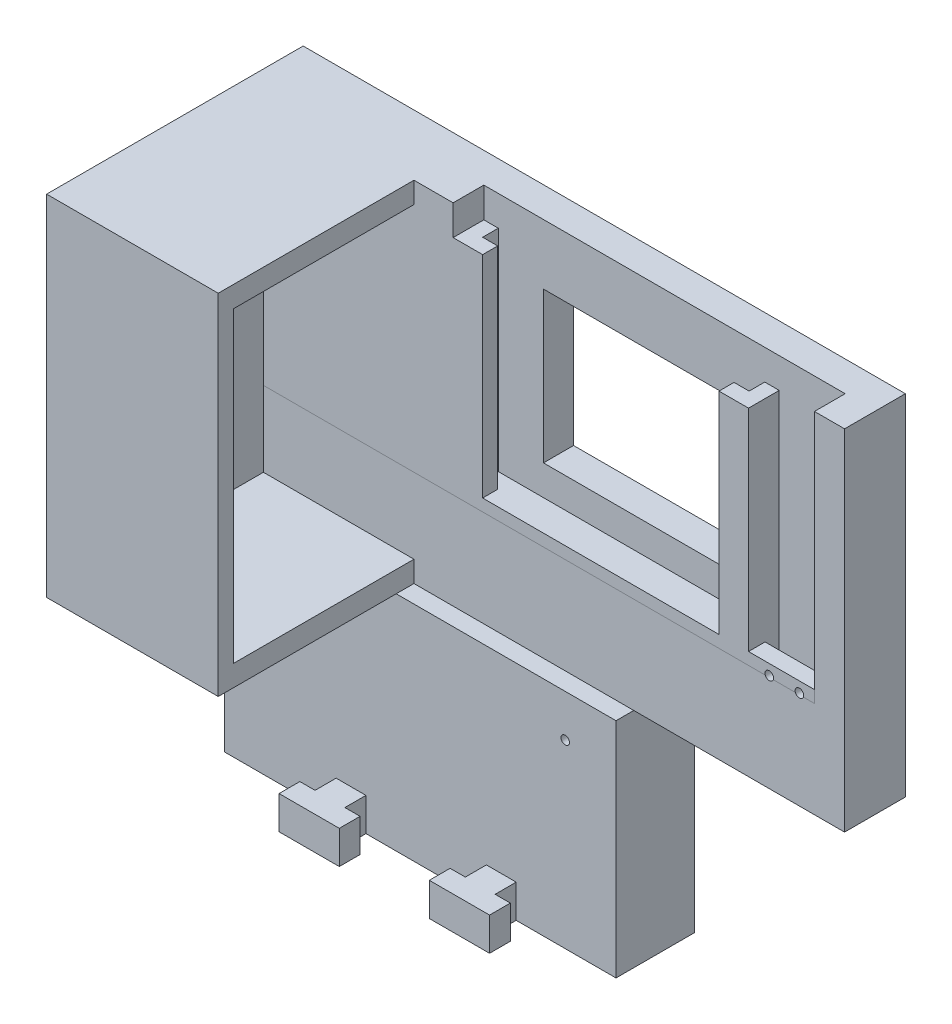
SolidWorks part; units mm, degrees
ref_plane "Front Plane" through (0, 0, 0) normal (0, 0, 1) x (1, 0, 0)
ref_plane "Top Plane" through (0, 0, 0) normal (0, 1, 0) x (1, 0, 0)
ref_plane "Right Plane" through (0, 0, 0) normal (1, 0, 0) x (0, 0, -1)
sketch "Sketch1" plane through (0, 0, 0) normal (0, 0, 1) x (1, 0, 0)
  line L1 (-95, -40) -> (95, -40)
  line L2 (-95, -40) -> (-95, 40)
  line L3 (-95, 40) -> (95, 40)
  line L4 (95, -40) -> (95, 40)
  line L5 (-95, -40) -> (95, 40) construction
  line L6 (-95, 40) -> (95, -40) construction
  point P0 (0, 0)
  dimension "D1" = 0
  dimension "D2" = 190
  dimension "80" = 80
extrude "Boss-Extrude1" add sketch "Sketch1" along normal blind 10
sketch "Sketch2" plane through (0, -40, 0) normal (0, -1, 0) x (1, 0, 0)
  line L0 (-95, 10) -> (95, 10) construction
  line L1 (-25, 10) -> (-20.2, 10)
  line L2 (-25, 10) -> (-25, 15.2)
  line L3 (-25, 15.2) -> (-20.2, 15.2)
  line L4 (-20.2, 10) -> (-20.2, 15.2)
  line L5 (-25, 20.2) -> (-15.2, 20.2)
  line L6 (-25, 20.2) -> (-25, 15.2)
  line L7 (-25, 15.2) -> (-15.2, 15.2)
  line L8 (-15.2, 20.2) -> (-15.2, 15.2)
  line L9 (73.1, 10) -> (68.3, 10)
  line L10 (73.1, 10) -> (73.1, 15.2)
  line L11 (73.1, 15.2) -> (68.3, 15.2)
  line L12 (68.3, 10) -> (68.3, 15.2)
  line L13 (63.3, 20.2) -> (73.1, 20.2)
  line L14 (63.3, 20.2) -> (63.3, 15.2)
  line L15 (63.3, 15.2) -> (73.1, 15.2)
  line L16 (73.1, 20.2) -> (73.1, 15.2)
  line L17 (-95, 10) -> (-95, 0) construction
  dimension "D1" = 0
  dimension "D2" = 0
  dimension "D3" = 0
  dimension "D4" = 5.2
  dimension "D5" = 9.8
  dimension "D6" = 5
  dimension "D7" = 4.8
  dimension "D8" = 9.8
  dimension "D9" = 5
  dimension "D10" = 0
  dimension "D11" = 0
  dimension "D12" = 0
  dimension "D13" = 5.2
  dimension "D14" = 4.8
  dimension "D15" = 88.5
  dimension "D16" = 70
extrude "Boss-Extrude2" add sketch "Sketch2" against normal blind 70 contours L8 L5 L6 L3 L7 | L16 L13 L14 L15 L11 | L4 L3 L2 L1 | L10 L11 L12 L9 region at (-20.1, -40, 17.7) region at (68.2, -40, 17.7)
sketch "Sketch3" plane through (0, 0, 10) normal (0, 0, 1) x (1, 0, 0)
  line L0 (-20.2, -40) -> (68.3, -40) construction
  line L1 (53.3, -30) -> (-5.2, -30)
  line L2 (53.3, -30) -> (53.3, 20)
  line L3 (53.3, 20) -> (-5.2, 20)
  line L4 (-5.2, -30) -> (-5.2, 20)
  line L5 (63.3, 30) -> (63.3, -40) construction
  line L6 (-15.2, 30) -> (-15.2, -40) construction
  line L7 (73.1, 30) -> (68.3, 30) construction
  dimension "D1" = 10
  dimension "D2" = 10
  dimension "D3" = 10
  dimension "D4" = 10
extrude "Cut-Extrude1" cut sketch "Sketch3" against normal blind 10
sketch "Sketch5" plane through (0, -40, 0) normal (0, -1, 0) x (-1, 0, 0)
  line L0 (25, -20.2) -> (15.2, -20.2) construction
  line L1 (95, -20.2) -> (-95, -20.2)
  line L2 (95, -20.2) -> (95, 0)
  line L3 (95, 0) -> (-95, 0)
  line L4 (-95, -20.2) -> (-95, 0)
  line L5 (95, -10) -> (95, 0) construction
  line L7 (95, 0) -> (-95, 0) construction
  line L8 (-95, -10) -> (-95, 0) construction
  dimension "D1" = 0
  dimension "D2" = 0
  dimension "D3" = 0
  dimension "D4" = 0
extrude "Boss-Extrude3" add sketch "Sketch5" along normal blind 4
sketch "Sketch6" plane through (0, 0, 0) normal (0, 0, -1) x (-1, 0, 0)
  line L0 (95, -44) -> (-95, -44) construction
  line L1 (95, -44) -> (-95, -44)
  line L2 (95, -44) -> (95, 40)
  line L3 (95, 40) -> (-95, 40)
  line L4 (-95, -44) -> (-95, 40)
  line L5 (95, -150) -> (-105, -150)
  line L6 (95, -150) -> (95, 40)
  line L7 (95, 40) -> (-105, 40)
  line L8 (-105, -150) -> (-105, 40)
  line L9 (95, 40) -> (95, -44) construction
  line L10 (-95, 40) -> (95, 40) construction
  line L11 (-95, -44) -> (-95, 40) construction
  line M5 (-95, 40) -> (-95, -44)
  line M6 (-95, -44) -> (95, -44)
  line M7 (95, -44) -> (95, 40)
  dimension "D1" = 0
  dimension "D2" = 0
  dimension "D3" = 0
  dimension "D4" = 0
  dimension "D5" = 10
  dimension "D6" = 190
  dimension "D7" = 0
  dimension "D8" = 0
extrude "Boss-Extrude5" add sketch "Sketch6" against normal blind 20.1999 contours L8 L5 L6 L7 M7 M6 M5 region at (8.6207, -93.3793, 0)
sketch "Sketch7" plane through (0, 0, 20.1999) normal (0, 0, 1) x (1, 0, 0)
  line L0 (105, -150) -> (105, 40) construction
  line L1 (105, -76) -> (-95, -76)
  line L2 (105, -76) -> (105, -150)
  line L3 (105, -150) -> (-95, -150)
  line L4 (-95, -76) -> (-95, -150)
  line L5 (70.7614, -89.3834) -> (70.4933, -89.3834)
  line L6 (70.7614, -89.3834) -> (70.7614, -108.9872)
  line L7 (70.7614, -108.9872) -> (70.4933, -108.9872)
  line L8 (70.4933, -89.3834) -> (70.4933, -108.9872)
  line L9 (-95, -150) -> (105, -150) construction
  line L10 (-95, -150) -> (-95, -44) construction
  line L11 (95, -44) -> (-95, -44) construction
  dimension "D1" = 0
  dimension "D2" = 0
  dimension "D3" = 0
  dimension "D4" = 32
extrude "Boss-Extrude6" add sketch "Sketch7" along normal blind 5.9
sketch "Sketch8" plane through (0, -150, 0) normal (0, -1, 0) x (1, 0, 0)
  line L0 (-95, 26.0999) -> (105, 26.0999) construction
  line L1 (-57.95, 33.0999) -> (-48.05, 33.0999)
  line L2 (-57.95, 33.0999) -> (-57.95, 26.0999)
  line L3 (-57.95, 26.0999) -> (-48.05, 26.0999)
  line L4 (-48.05, 33.0999) -> (-48.05, 26.0999)
  line L5 (-8.05, 33.0999) -> (1.85, 33.0999)
  line L6 (-8.05, 33.0999) -> (-8.05, 26.0999)
  line L7 (-8.05, 26.0999) -> (1.85, 26.0999)
  line L8 (1.85, 33.0999) -> (1.85, 26.0999)
  line L9 (-63, 39.9999) -> (-43, 39.9999)
  line L10 (-63, 39.9999) -> (-63, 33.0999)
  line L11 (-63, 33.0999) -> (-43, 33.0999)
  line L12 (-43, 39.9999) -> (-43, 33.0999)
  line L13 (-13.1, 39.9999) -> (6.9, 39.9999)
  line L14 (-13.1, 39.9999) -> (-13.1, 33.0999)
  line L15 (-13.1, 33.0999) -> (6.9, 33.0999)
  line L16 (6.9, 39.9999) -> (6.9, 33.0999)
  line L17 (-95, 26.0999) -> (-95, 0) construction
  line M3 (105, 26.0999) -> (-95, 26.0999)
  dimension "D1" = 0
  dimension "D2" = 7
  dimension "D3" = 0
  dimension "D4" = 6.9
  dimension "D5" = 20
  dimension "D6" = 9.9
  dimension "D7" = 5.05
  dimension "D8" = 32
  dimension "D9" = 0
  dimension "D10" = 7
  dimension "D11" = 9.9
  dimension "D12" = 0
  dimension "D13" = 20
  dimension "D14" = 6.9
  dimension "D15" = 5.05
  dimension "D16" = 40
extrude "Boss-Extrude7" add sketch "Sketch8" against normal blind 11 contours L12 L9 L10 L11 L1 | L4 L1 L2 M3 | L16 L13 L14 L15 L5 | L8 L5 L6 M3 region at (-53, -150, 36.5499) region at (-53, -150, 29.5999) region at (-3.1, -150, 29.5999) region at (-3.1, -150, 36.5499)
sketch "Sketch21" plane through (0, -40, 0) normal (0, 1, 0) x (1, 0, 0)
  line L0 (95, -10) -> (95, -20.1999) construction
  line L1 (95, -14.7) -> (73.1, -14.7)
  line L2 (95, -14.7) -> (95, -10)
  line L3 (95, -10) -> (73.1, -10)
  line L4 (73.1, -14.7) -> (73.1, -10)
  line L5 (73.1, -10) -> (95, -10) construction
  line L6 (73.1, -20.2) -> (73.1, -10) construction
  dimension "D1" = 0
  dimension "D2" = 0
  dimension "D3" = 4.7
  dimension "D4" = 0
extrude "Cut-Extrude7" cut sketch "Sketch21" against normal blind 5.5
sketch "Sketch22" plane through (0, 0, 20.2) normal (0, 0, 1) x (1, 0, 0)
  line L0 (95, -40) -> (73.1, -40) construction
  line L1 (95, -40) -> (95, -44) construction
  circle A0 centre (90, -43.5) radius 1.425
  circle A1 centre (80, -43.5) radius 1.425
  dimension "D1" = 2.85
  dimension "D2" = 2.85
  dimension "D4" = 3.5
  dimension "D3" = 3.5
  dimension "D5" = 5
  dimension "D6" = 10
extrude "Cut-Extrude8" cut sketch "Sketch22" against normal blind 5.5
sketch "Sketch23" plane through (0, 0, 10) normal (0, 0, 1) x (1, 0, 0)
  line L0 (-25, 30) -> (-25, -40) construction
  line L1 (-25, -40) -> (-95, -40)
  line L2 (-25, -40) -> (-25, 40)
  line L3 (-25, 40) -> (-95, 40)
  line L4 (-95, -40) -> (-95, 40)
  line L5 (-95, -40) -> (-25, -40) construction
  line L6 (-95, 40) -> (-95, -40) construction
  line L7 (95, 40) -> (-95, 40) construction
  dimension "D1" = 0
  dimension "D2" = 0
  dimension "D3" = 0
  dimension "D4" = 0
extrude "Boss-Extrude8" add sketch "Sketch23" along normal blind 10.2
sketch "Sketch24" plane through (0, 0, 26.0999) normal (0, 0, 1) x (1, 0, 0)
  line L0 (105, -150) -> (105, -76) construction
  line L1 (105, -150) -> (35, -150)
  line L2 (105, -150) -> (105, -76)
  line L3 (105, -76) -> (35, -76)
  line L4 (35, -150) -> (35, -76)
  line L5 (105, -76) -> (-95, -76) construction
  line L6 (1.85, -150) -> (105, -150) construction
  dimension "D1" = 0
  dimension "D2" = 0
  dimension "D3" = 0
  dimension "D4" = 70
extrude "Cut-Extrude9" cut sketch "Sketch24" against normal through all
sketch "Sketch25" plane through (0, 0, 20.2) normal (0, 0, 1) x (1, 0, 0)
  line L1 (-38, 40) -> (-95, 40)
  line L2 (-38, 40) -> (-38, 33)
  line L3 (-38, 33) -> (-95, 33)
  line L4 (-95, 40) -> (-95, 33)
  line L5 (-88, 33) -> (-95, 33)
  line L6 (-88, 33) -> (-88, -76)
  line L7 (-88, -76) -> (-95, -76)
  line L8 (-95, 33) -> (-95, -76)
  line L9 (-25, 40) -> (-95, 40) construction
  line L10 (-95, -44) -> (-95, 40) construction
  line L11 (35, -76) -> (-95, -76) construction
  line L13 (-38, -76) -> (-88, -76)
  line L14 (-38, -76) -> (-38, -69)
  line L15 (-38, -69) -> (-88, -69)
  line L16 (-88, -76) -> (-88, -69)
  dimension "D2" = 57
  dimension "D3" = 0
  dimension "D4" = 0
  dimension "D5" = 0
  dimension "D6" = 0
  dimension "D7" = 7
  dimension "D8" = 0
  dimension "D9" = 0
  dimension "D10" = 0
  dimension "D11" = 7
  dimension "D12" = 50
  dimension "D13" = 7
extrude "Boss-Extrude10" add sketch "Sketch25" along normal blind 60 contours L14 L15 L6 L13 | L3 L4 L1 L2 | L6 L7 L8 L5 region at (-63, -72.5, 20.2)
sketch "Sketch26" plane through (0, 0, 80.2) normal (0, 0, 1) x (1, 0, 0)
  line L0 (-38, -76) -> (-95, -76) construction
  line L1 (-38, -76) -> (-95, -76)
  line L2 (-38, -76) -> (-38, 40)
  line L3 (-38, 40) -> (-95, 40)
  line L4 (-95, -76) -> (-95, 40)
  line L5 (-38, -76) -> (-38, -69) construction
  line L6 (-95, 40) -> (-95, -76) construction
  line L7 (-38, 40) -> (-95, 40) construction
  dimension "D1" = 0
  dimension "D2" = 0
  dimension "D3" = 0
  dimension "D4" = 0
extrude "Boss-Extrude11" add sketch "Sketch26" along normal blind 5
sketch "Sketch27" plane through (0, -150, 0) normal (0, -1, 0) x (-1, 0, 0)
  line L0 (-1.85, -26.0999) -> (-35, -26.0999) construction
  line L1 (-6.9, -39.9999) -> (-6.9, -33.0999) construction
  line L2 (95, -26.0999) -> (57.95, -26.0999) construction
  line L3 (63, -39.9999) -> (63, -33.0999) construction
  circle A0 centre (-18.5, -16.0999) radius 1.4
  circle A1 centre (74.6, -16.0999) radius 1.4
  dimension "D1" = 2.8
  dimension "D2" = 2.8
  dimension "D3" = 10
  dimension "D4" = 11.6
  dimension "D5" = 10
  dimension "D6" = 11.6
extrude "Cut-Extrude10" cut sketch "Sketch27" against normal blind 10
sketch "Sketch28" plane through (0, 0, 26.0999) normal (0, 0, 1) x (1, 0, 0)
  line L0 (1.85, -150) -> (35, -150) construction
  line L1 (-95, -150) -> (-57.95, -150) construction
  line L2 (35, -76) -> (35, -150) construction
  line L3 (-95, -76) -> (-95, -150) construction
  circle A0 centre (18.14, -90) radius 1.4
  circle A1 centre (-78.14, -90) radius 1.4
  dimension "D1" = 60
  dimension "D2" = 60
  dimension "D3" = 16.86
  dimension "D4" = 2.8
  dimension "D5" = 2.8
  dimension "D6" = 16.86
extrude "Cut-Extrude11" cut sketch "Sketch28" against normal blind 10
split "Split1" bodies to split 136 resulting bodies 133 134 split by face at (-32.6667, -76, 22.1666)
